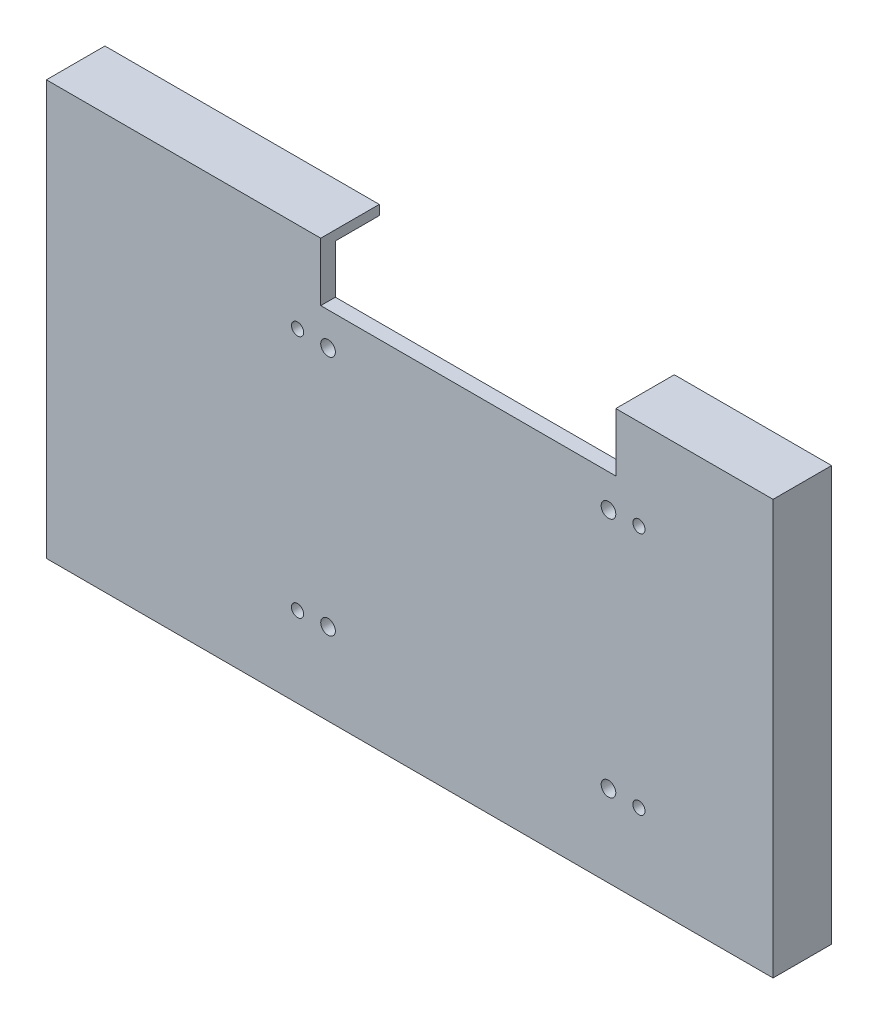
SolidWorks part; units mm, degrees
ref_plane "前视基准面" through (0, 0, 0) normal (0, 0, 1) x (1, 0, 0)
ref_plane "上视基准面" through (0, 0, 0) normal (0, 1, 0) x (1, 0, 0)
ref_plane "右视基准面" through (0, 0, 0) normal (1, 0, 0) x (0, 0, -1)
sketch "草图1" plane through (0, 0, 0) normal (0, 0, 1) x (1, 0, 0)
  line L0 (0, 24.75) -> (0, -24.75) construction
  line L1 (-28.75, -24.75) -> (28.75, -24.75) construction
  line L2 (-28.75, -24.75) -> (-28.75, 24.75) construction
  line L3 (-28.75, 24.75) -> (28.75, 24.75) construction
  line L4 (28.75, -24.75) -> (28.75, 24.75) construction
  line L5 (-28.75, -24.75) -> (28.75, 24.75) construction
  line L6 (-28.75, 24.75) -> (28.75, -24.75) construction
  line L7 (-28.75, 0) -> (28.75, 0) construction
  line L8 (-86.5, 43.5) -> (62.5, 43.5)
  line L9 (-84.5, 41.5) -> (60.5, 41.5)
  line L10 (-84.5, 41.5) -> (-84.5, -39.5)
  line L11 (-84.5, -39.5) -> (60.5, -39.5)
  line L12 (60.5, 41.5) -> (60.5, -39.5)
  line L13 (62.5, 43.5) -> (62.5, -41.5)
  line L14 (-86.5, -41.5) -> (62.5, -41.5)
  line L15 (-86.5, 43.5) -> (-86.5, -41.5)
  line L17 (-30.25, 43.5) -> (30.25, 43.5)
  line L18 (-30.25, 43.5) -> (-30.25, 31.5205)
  line L19 (-30.25, 31.5205) -> (30.25, 31.5205)
  line L20 (30.25, 43.5) -> (30.25, 31.5205)
  line L21 (-86.5, -15) -> (-63.6601, -15)
  line L22 (-86.5, -15) -> (-86.5, -30)
  line L23 (-86.5, -30) -> (-63.6601, -30)
  line L24 (-63.6601, -15) -> (-63.6601, -30)
  circle A0 centre (-28.75, 24.75) radius 1.5
  circle A1 centre (28.75, 24.75) radius 1.5
  circle A2 centre (28.75, -24.75) radius 1.5
  circle A3 centre (-28.75, -24.75) radius 1.5
  circle A4 centre (-35, 25) radius 1.25
  circle A5 centre (35, 25) radius 1.25
  circle A6 centre (35, -25) radius 1.25
  circle A7 centre (-35, -25) radius 1.25
  point P0 (0, 0)
  point P32 (0, 0)
  point P33 (-43.5234, 24.75)
  point P34 (0, 0)
  point P35 (0, 0)
  dimension "D3" = 3
  dimension "D11" = 2.5
  dimension "D13" = 25
  dimension "D1" = 57.5
  dimension "D2" = 49.5
  dimension "D4" = 14.75
  dimension "D5" = 31.75
  dimension "D6" = 16.75
  dimension "D7" = 55.75
  dimension "D9" = 15
  dimension "D10" = 9.5
  dimension "D12" = 35
  dimension "D8" = 2
extrude "凸台-拉伸2" add sketch "草图1" against normal blind 3 contours L12 L9 L10 L11 A1 A0 A2 A3 region at (-10.9253, -0.3028, 0)
extrude "凸台-拉伸3" add sketch "草图1<3>" against normal blind 12 contours L8 L15 L14 L13 L9 L12 L11 L10 | L15 L21 L10 L9 L18 L8 region at (-58.375, 42.6884, 0) region at (46.375, 41.7846, 0)
sketch "草图1<3>" plane through (0, 0, 0) normal (0, 0, 1) x (1, 0, 0) same geometry as "草图1"
extrude "凸台-拉伸4" add sketch "草图1<4>" against normal blind 1 from surface contours L24 L21 L10 L23 | L15 L23 L10 L21 region at (-85.5, -22.5, 0) region at (-74.08, -22.5, 0) starting at face at (-29.0267, 5.3368, 0)
sketch "草图1<4>" plane through (0, 0, 0) normal (0, 0, 1) x (1, 0, 0) same geometry as "草图1"
